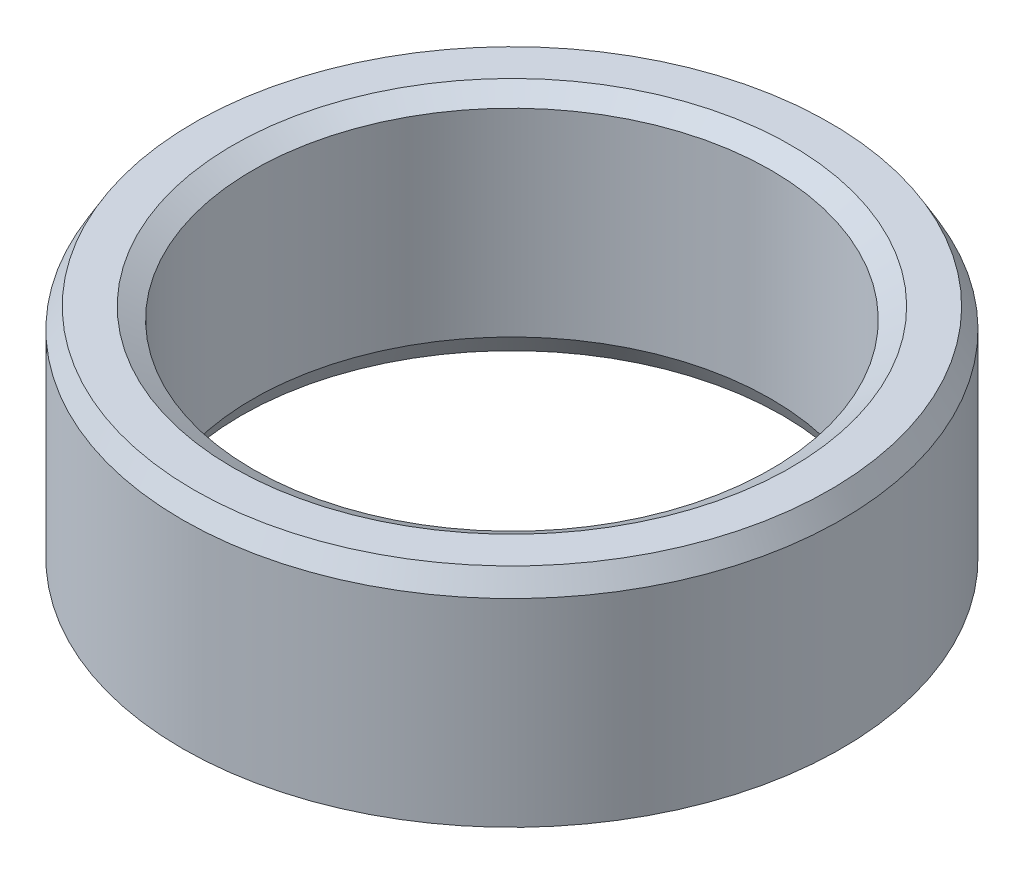
SolidWorks part; units mm, degrees
ref_plane "Front Plane" through (0, 0, 0) normal (0, 0, 1) x (1, 0, 0)
ref_plane "Top Plane" through (0, 0, 0) normal (0, 1, 0) x (1, 0, 0)
ref_plane "Right Plane" through (0, 0, 0) normal (1, 0, 0) x (0, 0, -1)
sketch "Sketch1" plane through (0, 0, 0) normal (0, 1, 0) x (1, 0, 0)
  circle A0 centre (0, 0) radius 35
  dimension "SLEEVE_OD" = 70
extrude "Boss-Extrude1" add sketch "Sketch1" along normal blind 24.4
sketch "Sketch2" plane through (0, 0, 0) normal (0, 1, 0) x (1, 0, 0)
  circle A0 centre (0, 0) radius 27.5119
  dimension "BORE_D" = 55.0239
extrude "Cut-Extrude1" cut sketch "Sketch2" along normal through all
chamfer "Chamfer1" distance 2.1301 angle 30 4 edges at (0, 24.4, 27.5119) (0, 0, 27.5119) (0, 0, 35) (0, 24.4, 35) first distance on face at (0, 24.4, 27.5119) first distance on face at (0, 0, 27.5119) first distance on face at (0, 24.4, 35)
